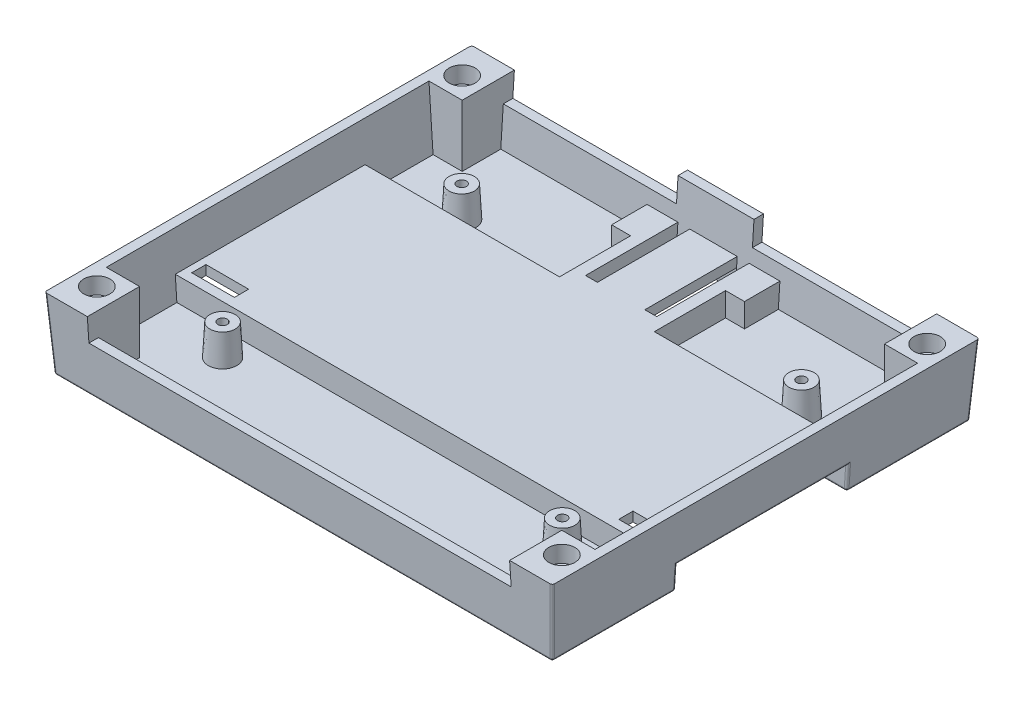
SolidWorks part; units mm, degrees
ref_plane "Спереди" through (0, 0, 0) normal (0, 0, 1) x (1, 0, 0)
ref_plane "Сверху" through (0, 0, 0) normal (0, 1, 0) x (1, 0, 0)
ref_plane "Справа" through (0, 0, 0) normal (1, 0, 0) x (0, 0, -1)
sketch "Эскиз1" plane through (0, 0, 0) normal (1, 0, 0) x (0, 0, -1)
  line L0 (0, -10) -> (0, 0) construction
  line L1 (18, -15) -> (44, -15)
  line L2 (44, -15) -> (45, 0)
  line L3 (45, 0) -> (-45, 0)
  line L4 (18, -15) -> (18, -10)
  line L5 (18, -10) -> (-18, -10)
  line L6 (-18, -15) -> (-18, -10)
  line L7 (-44, -15) -> (-45, 0)
  line L8 (-18, -15) -> (-44, -15)
  line L11 (-16.5, -11.5) -> (-18, -14.5)
  line L12 (-18, -11.5) -> (-16.5, -11.5)
  dimension "D1" = 36
  dimension "D2" = 5
  dimension "D3" = 15
  dimension "D4" = 90
  dimension "D5" = 88
  dimension "D6" = 1.5
  dimension "D7" = 1.5
  dimension "D8" = 3
extrude "Бобышка-Вытянуть1" add sketch "Эскиз1" along normal blind 107 contours L4 | L5 L0 L3 L7 L8 L6 | L0 L5 L4 L1 L2 L3 region at (0, -6.6883, 24.316) region at (0, -6.6883, -24.316)
sketch "Эскиз3" plane through (0, 0, 0) normal (0, 0, 1) x (1, 0, 0)
  line L0 (0, 0) -> (1, -15)
  line L1 (107, -15) -> (0, -15) construction
  line L2 (1, -15) -> (106, -15)
  line L3 (106, -15) -> (107, 0)
  line L4 (107, 0) -> (0, 0)
  line L5 (53.5, 0) -> (53.5, -15) construction
  line L6 (107, 0) -> (0, 0) construction
  dimension "D2" = 3.814
extrude "Вырез-Вытянуть2" cut sketch "Эскиз3" against normal through all and the other way through all flip side to cut
fillet "Скругление2" radius 0.5 18 edges at (53.5, -15, -18) (53.5, -15, -44) (53.5, -15, 44) (53.5, -15, 18) (1, -15, -31) (106, -15, -31) (1, -15, 31) (106, -15, 31) (106.1667, -12.5, -18) (106.3333, -10, 0) (106.1667, -12.5, 18) (0.8333, -12.5, 18) (0.6667, -10, 0) (0.8333, -12.5, -18) (0.5, -7.5, -44.5) (106.5, -7.5, -44.5) (106.5, -7.5, 44.5) (0.5, -7.5, 44.5)
shell "Оболочка3" thickness 2 removed face at (53.5, 0, 0)
sketch "Эскиз4" plane through (0, 0, 0) normal (0, 1, 0) x (1, 0, 0)
  line L0 (0, 0) -> (107, 0) construction
  line L1 (107, 44.5011) -> (107, -44.5011) construction
  line L2 (53.5, -45) -> (53.5, 45) construction
  line L3 (106.5011, -45) -> (0.4989, -45) construction
  line L4 (106.5011, 45) -> (0.4989, 45) construction
  line L5 (97.9956, 42.9956) -> (97.9956, 33.9956)
  line L6 (2.0044, 42.9956) -> (9.0044, 42.9956)
  line L7 (2.0044, 42.9956) -> (2.0044, 33.9956)
  line L8 (2.0044, 33.9956) -> (9.0044, 33.9956)
  line L9 (9.0044, 42.9956) -> (9.0044, 33.9956)
  line L10 (104.9956, 33.9956) -> (97.9956, 33.9956)
  line L11 (104.9956, 42.9956) -> (104.9956, 33.9956)
  line L12 (104.9956, 42.9956) -> (97.9956, 42.9956)
  line L13 (104.9956, -42.9956) -> (97.9956, -42.9956)
  line L14 (104.9956, -42.9956) -> (104.9956, -33.9956)
  line L15 (104.9956, -33.9956) -> (97.9956, -33.9956)
  line L16 (9.0044, -42.9956) -> (9.0044, -33.9956)
  line L17 (2.0044, -33.9956) -> (9.0044, -33.9956)
  line L18 (2.0044, -42.9956) -> (2.0044, -33.9956)
  line L19 (2.0044, -42.9956) -> (9.0044, -42.9956)
  line L20 (97.9956, -42.9956) -> (97.9956, -33.9956)
  dimension "D1" = 9
  dimension "D2" = 7
extrude "Бобышка-Вытянуть2" add sketch "Эскиз4" against normal up to surface (13 mm away) up to face at (53.5, -13, -31.0644)
sketch "Эскиз5" plane through (0, 0, 0) normal (0, 0, 1) x (1, 0, 0)
  line L0 (53.5, 0) -> (53.5, -5) construction
  line L1 (106.5011, 0) -> (0.4989, 0) construction
  line L2 (45.5, 0) -> (45.5, -5)
  line L3 (9.0044, 0) -> (97.9956, 0)
  line L4 (9.0044, 0) -> (9.0044, -5)
  line L5 (9.0044, -5) -> (97.9956, -5)
  line L6 (97.9956, 0) -> (97.9956, -5)
  line L7 (61.5, 0) -> (61.5, -5)
  dimension "D1" = 5
  dimension "D2" = 16
extrude "Вырез-Вытянуть3" cut sketch "Эскиз5" against normal through all contours L4 L5 L2 L3 | L3 L7 L5 L6 region at (27.2522, -2.5, 0) region at (79.7478, -2.5, 0)
extrude "Вырез-Вытянуть4" cut sketch "Эскиз5<5>" along normal through all contours L3 L7 L5 L6 | L3 L0 L5 L7 | L0 L3 L2 L5 | L4 L5 L2 L3 region at (57.5, -2.5, 0) region at (49.5, -2.5, 0) region at (27.2522, -2.5, 0) region at (79.7478, -2.5, 0)
sketch "Эскиз5<5>" plane through (0, 0, 0) normal (0, 0, 1) x (1, 0, 0) same geometry as "Эскиз5"
sketch "Эскиз6" plane through (0, 0, 0) normal (0, 1, 0) x (1, 0, 0)
  line L0 (53.5, 45) -> (53.5, 20) construction
  line L1 (61.5, 45) -> (45.5, 45) construction
  line L2 (104.4622, 20) -> (2.5378, 20) construction
  line L3 (63.5, 20) -> (63.5, 35)
  line L4 (2.8711, 20) -> (104.1289, 20) construction
  line L5 (63.5, 35) -> (67.5, 35)
  line L6 (67.5, 35) -> (67.5, 43)
  line L7 (67.5, 43) -> (39.5, 43)
  line L8 (63.5, 20) -> (43.5, 20)
  line L9 (39.5, 35) -> (39.5, 43)
  line L10 (43.5, 35) -> (39.5, 35)
  line L11 (43.5, 20) -> (43.5, 35)
  line L12 (46, 43) -> (46, 23)
  line L13 (58.5, 43) -> (61, 43)
  line L14 (58.5, 43) -> (58.5, 23)
  line L15 (58.5, 23) -> (61, 23)
  line L16 (61, 43) -> (61, 23)
  line L17 (48.5, 23) -> (46, 23)
  line L18 (48.5, 43) -> (48.5, 23)
  line L19 (48.5, 43) -> (46, 43)
  line L20 (46, 23) -> (43.5, 23)
  line L21 (61, 23) -> (63.5, 23)
  line L22 (46, 23) -> (46, 20)
  line L23 (43.5, 20) -> (63.5, 20)
  line L24 (46, 20) -> (61, 20)
  line L25 (46, 20) -> (46, 15)
  line L26 (46, 15) -> (61, 15)
  line L27 (61, 20) -> (61, 15)
  line L28 (61, 23) -> (61, 20)
  point P15 (53.5, 43)
  dimension "D1" = 23
  dimension "D2" = 8
  dimension "D3" = 28
  dimension "D4" = 20
  dimension "D5" = 10
  dimension "D6" = 2.5
  dimension "D7" = 3
  dimension "D9" = 5
extrude "Бобышка-Вытянуть4" add sketch "Эскиз6" against normal up to surface (13 mm away) from offset 8 contours L16 L21 L3 L5 L6 L7 | L21 L28 L8 L3 | L7 L0 L23 L28 L15 L14 | L0 L7 L18 L17 L22 L24 | L22 L20 L11 L8 | L20 L12 L7 L9 L10 L11 region at (56.2296, 0, -30.8878) region at (50.7704, 0, -30.8878) region at (62.25, 0, -21.5) region at (44.75, 0, -21.5) region at (63.5183, 0, -35.3415) region at (43.4817, 0, -35.3415) up to face at (53.5, -13, -32.53) offset against normal yes
extrude "Вырез-Вытянуть5" cut sketch "Эскиз6<4>" along normal up to surface (-10 mm away) from offset 20 contours L0 L7 L18 L17 L20 L11 L8 | L7 L0 L8 L3 L21 L15 L14 | L8 L23 region at (53.5, 0, -17.5) region at (53.5, 0, -30.8878) up to face at (53.5, -10, 0) offset against normal yes
sketch "Эскиз6<4>" plane through (0, 0, 0) normal (0, 1, 0) x (1, 0, 0) same geometry as "Эскиз6"
extrude "Бобышка-Вытянуть5" add sketch "Эскиз1<3>" along normal blind 107 contours L12 L6 L11 region at (0, -12.5, 17.5)
sketch "Эскиз1<3>" plane through (0, 0, 0) normal (1, 0, 0) x (0, 0, -1) same geometry as "Эскиз1"
sketch "Эскиз7" plane through (0, 0, 0) normal (0, 1, 0) x (1, 0, 0)
  line L0 (0, 0) -> (107, 0) construction
  line L1 (107, 44.5011) -> (107, -44.5011) construction
  line L2 (53.5, 0) -> (53.5, -18) construction
  line L3 (105.5322, -18) -> (1.4678, -18) construction
  line L4 (4, -18) -> (4, -15)
  line L5 (0, -18) -> (107, -18)
  line L6 (0, -18) -> (0, -15)
  line L7 (0, -15) -> (107, -15)
  line L8 (107, -18) -> (107, -15)
  line L9 (13, -18) -> (13, -15)
  line L10 (94, -18) -> (94, -15)
  line L11 (103, -18) -> (103, -15)
  dimension "D1" = 4
  dimension "D2" = 9
  dimension "D3" = 3
extrude "Вырез-Вытянуть6" cut sketch "Эскиз7" against normal through all from offset 10 contours L7 L6 L5 L4 | L5 L10 L7 L9 | L11 L5 L8 L7 region at (2, 0, 16.5) region at (53.5, 0, 16.5) region at (105, 0, 16.5) offset against normal yes
extrude "Вырез-Вытянуть7" cut sketch "Эскиз7<3>" against normal up to surface (11.5 mm away) contours L5 L11 L7 L10 | L5 L9 L7 L4 region at (8.5, 0, 16.5) region at (98.5, 0, 16.5) up to face at (8.5, -11.5, 17.25)
sketch "Эскиз7<3>" plane through (0, 0, 0) normal (0, 1, 0) x (1, 0, 0) same geometry as "Эскиз7"
sketch "Эскиз8" plane through (0, 0, 0) normal (0, 1, 0) x (1, 0, 0)
  line L0 (0, 0) -> (107, 0) construction
  line L1 (107, 44.5011) -> (107, -44.5011) construction
  line L2 (53.5, 45) -> (53.5, -47.2266) construction
  line L3 (61.5, 45) -> (45.5, 45) construction
  circle A0 centre (4.5, 38.5) radius 2.75
  circle A1 centre (4.5, 38.5) radius 1.25
  circle A2 centre (102.5, 38.5) radius 1.25
  circle A3 centre (102.5, 38.5) radius 2.75
  circle A4 centre (102.5, -38.5) radius 2.75
  circle A5 centre (102.5, -38.5) radius 1.25
  circle A6 centre (4.5, -38.5) radius 1.25
  circle A7 centre (4.5, -38.5) radius 2.75
  dimension "D1" = 5.5
  dimension "D2" = 2.5
extrude "Вырез-Вытянуть8" cut sketch "Эскиз8" against normal blind 3.5 contours A0 | A3 | A7 | A4
extrude "Вырез-Вытянуть9" cut sketch "Эскиз8<3>" against normal blind 12 draft 2 contours A2 | A1 | A6 | A5 region at (4.5, 0, -38.5) region at (102.5, 0, -38.5) region at (102.5, 0, 38.5) region at (4.5, 0, 38.5)
sketch "Эскиз8<3>" plane through (0, 0, 0) normal (0, 1, 0) x (1, 0, 0) same geometry as "Эскиз8"
sketch "Эскиз9" plane through (0, 0, 0) normal (0, 1, 0) x (1, 0, 0)
  line L0 (17.7, 0) -> (89.3, 0) construction
  line L1 (17.7, -25.2) -> (89.3, -25.2) construction
  line L2 (17.7, -25.2) -> (17.7, 25.2) construction
  line L3 (17.7, 25.2) -> (89.3, 25.2) construction
  line L4 (89.3, -25.2) -> (89.3, 25.2) construction
  line L5 (53.5, 25.2) -> (53.5, -25.2) construction
  line L6 (61.5, 45) -> (45.5, 45) construction
  circle A0 centre (17.7, 25.2) radius 3
  circle A1 centre (17.7, 25.2) radius 1
  circle A2 centre (89.3, 25.2) radius 1
  circle A3 centre (89.3, 25.2) radius 3
  circle A4 centre (89.3, -25.2) radius 3
  circle A5 centre (89.3, -25.2) radius 1
  circle A6 centre (17.7, -25.2) radius 1
  circle A7 centre (17.7, -25.2) radius 3
  point P8 (53.5, 45)
  dimension "D3" = 6
  dimension "D4" = 2
  dimension "D1" = 50.4
  dimension "D2" = 71.6
extrude "Бобышка-Вытянуть6" add sketch "Эскиз9" along normal blind 6.5 draft 3 from offset 13 contours A0 | A3 | A4 | A7 offset against normal yes
extrude "Вырез-Вытянуть10" cut sketch "Эскиз9<3>" against normal offset from surface (13 mm away) 2 contours A1 | A2 | A5 | A6 region at (17.7, 0, -25.2) region at (89.3, 0, -25.2) region at (89.3, 0, 25.2) region at (17.7, 0, 25.2) up to face at (53.5, -15, 31.0161)
sketch "Эскиз9<3>" plane through (0, 0, 0) normal (0, 1, 0) x (1, 0, 0) same geometry as "Эскиз9"
